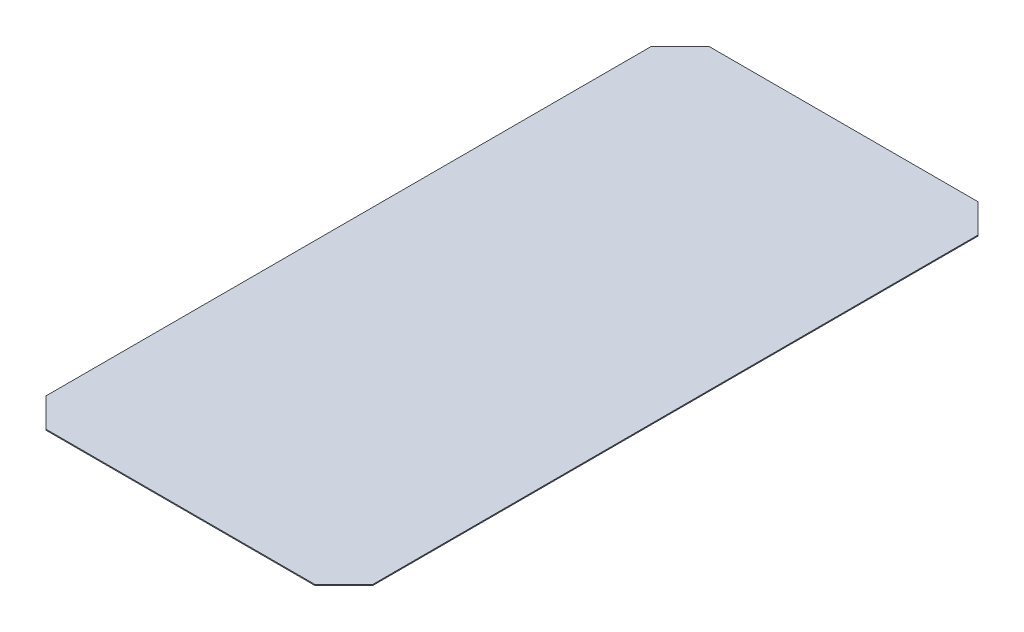
SolidWorks part; units mm, degrees
ref_plane "Front Plane" through (0, 0, 0) normal (0, 0, 1) x (1, 0, 0)
ref_plane "Top Plane" through (0, 0, 0) normal (0, 1, 0) x (1, 0, 0)
ref_plane "Right Plane" through (0, 0, 0) normal (1, 0, 0) x (0, 0, -1)
ref_axis "X-Axis" through (-88.99, 0, 0) along (1, 0, 0)
ref_axis "Y-Axis" through (0, 55, 0) along (0, -1, 0)
ref_axis "Z-Axis" through (0, 0, -88.99) along (0, 0, 1)
sketch "Sketch1" plane through (0, 0, 0) normal (0, 1, 0) x (1, 0, 0)
  line L1 (-24.1, -40) -> (24.1, -40)
  line L2 (-24.1, -40) -> (-24.1, 40)
  line L3 (-24.1, 40) -> (24.1, 40)
  line L4 (24.1, -40) -> (24.1, 40)
  line L5 (-24.1, -40) -> (24.1, 40) construction
  line L6 (-24.1, 40) -> (24.1, -40) construction
  point P0 (0, 0)
  dimension "D1" = 48.2
  dimension "D2" = 80
extrude "Boss-Extrude1" add sketch "Sketch1" along normal blind 0.1
sketch "Sketch2" plane through (0, 0.1, 0) normal (0, 1, 0) x (1, 0, 0)
  line L0 (9.9, 40) -> (24.1, 40)
  line L1 (-24.1, 40) -> (9.9, 40) construction
  line L2 (-24.1, 40) -> (-24.1, -29) construction
  line L3 (-24.1, -29) -> (9.9, -29)
  line L4 (9.9, 40) -> (9.9, -29)
  line L5 (24.1, 40) -> (24.1, -40)
  line L6 (24.1, -40) -> (-24.1, -40)
  line L7 (-24.1, -40) -> (-24.1, -29)
  dimension "D1" = 34
  dimension "D2" = 69
extrude "Cut-Extrude1" cut sketch "Sketch2" against normal through all
chamfer "Chamfer1" distance 3 angle 45 4 edges at (9.9, 0.05, -40) (-24.1, 0.05, -40) (9.9, 0.05, 29) (-24.1, 0.05, 29)
